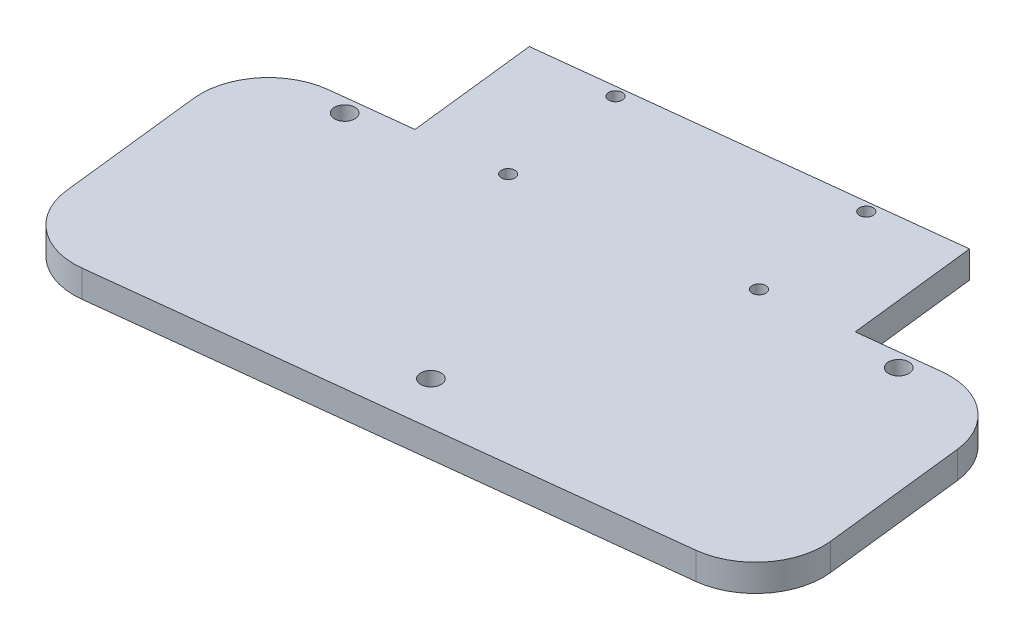
SolidWorks part; units mm, degrees
ref_plane "Front Plane" through (0, 0, 0) normal (0, 0, 1) x (1, 0, 0)
ref_plane "Top Plane" through (0, 0, 0) normal (0, 1, 0) x (1, 0, 0)
ref_plane "Right Plane" through (0, 0, 0) normal (1, 0, 0) x (0, 0, -1)
sketch "Sketch1" plane through (0, 0, 0) normal (0, 1, 0) x (1, 0, 0)
  line L0 (4.9161, -180.9962) -> (11.7351, -241.0893) construction
  line L1 (-43.5958, -205.8072) -> (-22.1351, -203.372)
  line L2 (-22.1351, -203.372) -> (-24.298, -184.3112)
  line L3 (-24.298, -184.3112) -> (34.1302, -177.6811)
  line L4 (34.1302, -177.6811) -> (36.2931, -196.7419)
  line L8 (36.2931, -196.7419) -> (57.7538, -194.3067)
  line L9 (57.7538, -194.3067) -> (62.4099, -235.339)
  line L10 (62.4099, -235.339) -> (-38.9397, -246.8395)
  line L11 (-38.9397, -246.8395) -> (-43.5958, -205.8072)
  line L12 (11.2789, -179.7828) -> (11.2789, 11.1383) construction
  line L13 (-11.565, -184.3131) -> (21.7214, -180.536) construction
  circle A0 centre (-29.4314, -206.4643) radius 1.5
  circle A1 centre (44.0967, -198.1208) radius 1.5
  circle A2 centre (10.9407, -234.0885) radius 1.5
  circle A3 centre (10.9407, -234.0885) radius 1.5 construction
  circle A4 centre (-9.536, -202.1939) radius 1
  circle A5 centre (-11.565, -184.3131) radius 1
  circle A6 centre (21.7214, -180.536) radius 1
  circle A10 centre (44.0967, -198.1208) radius 1.5 construction
  circle A11 centre (23.7504, -198.4167) radius 1
  dimension "D6" = 3
  dimension "D1" = 102
extrude "Boss-Extrude1" add sketch "Sketch1" along normal blind 4
fillet "Fillet1" radius 10 1 edges at (-38.9397, 2, 246.8395)
fillet "Fillet2" radius 10 1 edges at (62.4099, 2, 235.339)
fillet "Fillet3" radius 10 1 edges at (57.7538, 2, 194.3067)
fillet "Fillet4" radius 10 1 edges at (-43.5958, 2, 205.8072)
